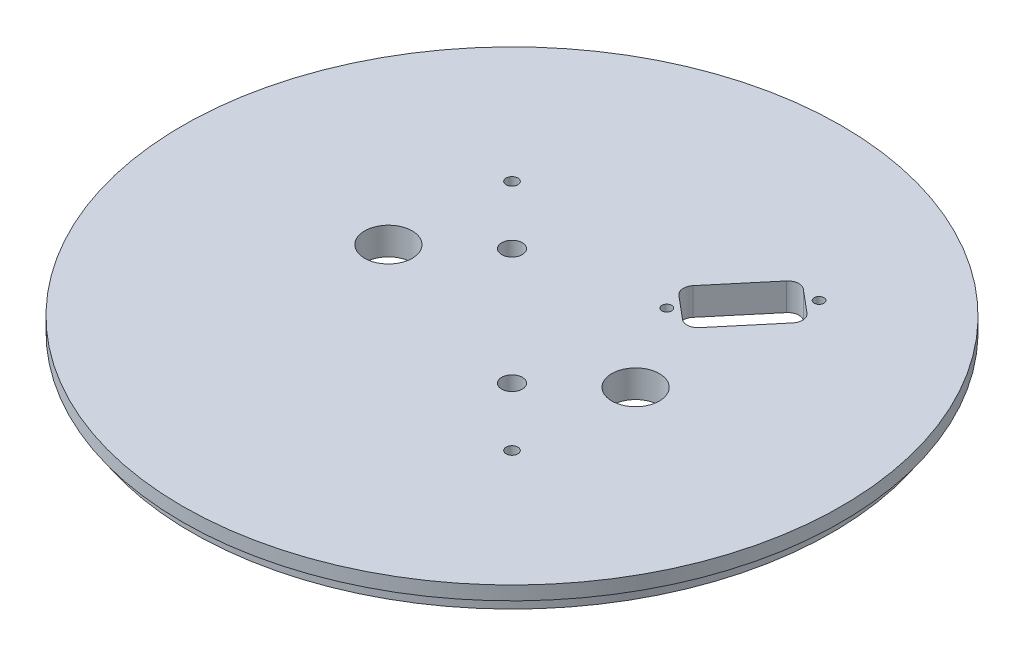
SolidWorks part; units mm, degrees
material "6061-T6 (SS)"
ref_plane "Front Plane" through (0, 0, 0) normal (0, 0, 1) x (1, 0, 0)
ref_plane "Top Plane" through (0, 0, 0) normal (0, 1, 0) x (1, 0, 0)
ref_plane "Right Plane" through (0, 0, 0) normal (1, 0, 0) x (0, 0, -1)
sketch "Sketch1" plane through (0, 0, 0) normal (0, 1, 0) x (1, 0, 0)
  line L0 (0, -76.2) -> (0, 76.2) construction
  line L1 (-76.2, 0) -> (76.2, 0) construction
  line L2 (-26.9408, 26.9408) -> (0, 0) construction
  line L3 (0, 56.7387) -> (0, 29.6936) construction
  line L4 (3.6407, 56.7387) -> (3.6407, 29.6936) construction
  line L5 (-3.6407, 56.7387) -> (-3.6407, 29.6936) construction
  line L6 (0, -56.7387) -> (0, -29.6936) construction
  line L7 (3.6407, -56.7387) -> (3.6407, -29.6936) construction
  line L8 (-3.6407, -56.7387) -> (-3.6407, -29.6936) construction
  line L9 (-53.8815, -53.8815) -> (54.3236, 54.3236) construction
  circle A0 centre (0, 0) radius 76.2
  circle A1 centre (0, 0) radius 3.175 construction
  circle A2 centre (28.575, 0) radius 5.5
  circle A3 centre (-28.575, 0) radius 5.5
  circle A4 centre (-26.9408, 26.9408) radius 1.3589
  arc A6 (3.6407, 56.7387) -> (-3.6407, 56.7387) centre (0, 56.7387) ccw construction
  arc A7 (-3.6407, 29.6936) -> (3.6407, 29.6936) centre (0, 29.6936) ccw construction
  arc A8 (3.6407, -56.7387) -> (-3.6407, -56.7387) centre (0, -56.7387) cw construction
  arc A9 (-3.6407, -29.6936) -> (3.6407, -29.6936) centre (0, -29.6936) cw construction
  circle A10 centre (26.9408, -26.9408) radius 1.3589
  circle A11 centre (-13.4704, 13.4704) radius 2.3813
  circle A12 centre (13.4704, -13.4704) radius 2.3813
  point P16 (0, 43.2162)
  point P19 (0, 0)
  point P26 (0, -43.2162)
  dimension "D1" = 152.4
  dimension "D2" = 6.35
  dimension "D3" = 11
  dimension "D5" = 2.7178
  dimension "D8" = 4.7625
  dimension "D6" = 38.1
  dimension "D7" = 45
  dimension "D4" = 45
  dimension "D9" = 28.575
extrude "Boss-Extrude1" add sketch "Sketch1" along normal blind 6.35
sketch "Sketch2" plane through (0, 0, 0) normal (0, -1, 0) x (1, 0, 0)
  circle A0 centre (0, 0) radius 76.2
  circle A1 centre (0, 0) radius 74.041
  dimension "D1" = 152.4
  dimension "D2" = 148.082
extrude "Cut-Extrude1" cut sketch "Sketch2" against normal blind 3.175
sketch "Sketch3" plane through (0, 6.35, 0) normal (0, 1, 0) x (1, 0, 0)
  line L0 (0, 76.2) -> (0, -76.2) construction
  line L1 (-76.2, 0) -> (76.2, 0) construction
  line L2 (0, 34.798) -> (0, 13.97) construction
  line L3 (3.2385, 34.798) -> (3.2385, 13.97)
  line L4 (-3.2385, 34.798) -> (-3.2385, 13.97)
  line L5 (0, -34.798) -> (0, -13.97) construction
  line L6 (3.2385, -34.798) -> (3.2385, -13.97)
  line L7 (-3.2385, -34.798) -> (-3.2385, -13.97)
  circle A0 centre (0, 0) radius 76.2 construction
  arc A1 (3.2385, 34.798) -> (-3.2385, 34.798) centre (0, 34.798) ccw
  arc A2 (-3.2385, 13.97) -> (3.2385, 13.97) centre (0, 13.97) ccw
  arc A3 (3.2385, -34.798) -> (-3.2385, -34.798) centre (0, -34.798) cw
  arc A4 (-3.2385, -13.97) -> (3.2385, -13.97) centre (0, -13.97) cw
  point P7 (0, 13.97)
  point P8 (0, 34.798)
  point P12 (0, 24.384)
  point P20 (0, -24.384)
  point P25 (0, -34.798)
  point P26 (0, -13.97)
  dimension "D1" = 13.97
  dimension "D2" = 20.828
  dimension "D3" = 6.477
extrude "Cut-Extrude2" cut sketch "Sketch3" against normal blind 3.556 from offset 5.969 offset against normal yes
hole_wizard "Tap Drill for #4-40 Tap1" positions "Sketch5" profile "Sketch6" hole size "#4-40" standard "ANSI Inch" end condition through all
sketch "Sketch5" plane through (0, 6.35, 0) normal (0, 1, 0) x (1, 0, 0)
  line L0 (0, 0) -> (53.6567, 63.9455) construction
  line L2 (0, 0) -> (28.575, 0) construction
  point P0 (16.3268, 19.4575)
  point P2 (32.3965, 38.6086)
  dimension "D1" = 50
  dimension "D2" = 25
  dimension "D3" = 25.4
sketch "Sketch6" plane through (16.3268, 6.35, -19.4575) normal (1, 0, 0) x (0, 0, 1)
  line L0 (0, 0) -> (0, 6.35)
  line L1 (0, 6.35) -> (1.1303, 6.35)
  line L2 (1.1303, 6.35) -> (1.1303, 0)
  line L5 (1.1303, 0) -> (0, 0)
  line L11 (0, -6.35) -> (0, 107.95) construction
  dimension "Thru Hole Dia." = 2.2606
  dimension "Thru Hole Depth" = 6.35
sketch "Sketch4" plane through (0, 6.35, 0) normal (0, 1, 0) x (1, 0, 0)
  line L0 (15.1695, 23.4128) -> (20.423, 19.0046)
  line L1 (14.8564, 26.9913) -> (24.7219, 38.7485)
  line L2 (24.0014, 19.3177) -> (33.8669, 31.0749)
  line L3 (28.3003, 39.0616) -> (33.5538, 34.6533)
  line L4 (0, 0) -> (32.3965, 38.6086) construction
  circle A1 centre (16.3268, 19.4575) radius 1.1303 construction
  arc A2 (24.7219, 38.7485) -> (28.3003, 39.0616) centre (26.6676, 37.1158) cw
  arc A3 (33.8669, 31.0749) -> (33.5538, 34.6533) centre (31.9212, 32.7076) ccw
  arc A4 (20.423, 19.0046) -> (24.0014, 19.3177) centre (22.0557, 20.9503) ccw
  arc A5 (14.8564, 26.9913) -> (15.1695, 23.4128) centre (16.8021, 25.3586) ccw
  point P11 (17.7962, 21.2087)
  dimension "D4" = 2.54
  dimension "D1" = 2.286
  dimension "D2" = 2.286
  dimension "D3" = 11.938
extrude "Cut-Extrude3" cut sketch "Sketch4" against normal through all
equation "\"leadDist\"=1.5"
equation "\"Lead_Screw_Dist\"= 2.25in"
equation "\"D9@Sketch1\"=\"Lead_Screw_Dist\"/2"
equation "\"Lead_Screw_Diam\"= 11mm"
equation "\"D3@Sketch1\"=\"Lead_Screw_Diam\""
equation "\"Bodytube_OD\"= 6.17in"
equation "\"Bodytube_ID\"= 5.998in"
equation "\"Motor_OD\"= 4in"
equation "\"Fwd_Tube_Length\"= 40in"
equation "\"Mid_Tube_Length\"= 1in"
equation "\"Aft_Section_Length\"= 39in"
equation "\"AB_Coupler_OD_Length\"= 1in"
equation "\"AB_Coupling_Section_Length\"= 0.375in"
equation "\"AB_Coupler_Length\"= \"AB_Coupler_OD_Length\" + \"AB_Coupling_Section_Length\" * 2"
equation "\"Cutout_Angle\"= 80"
equation "\"AB_Paddle_Height\"= 0.375in"
equation "\"AB_Coupler_Num_Screws\"= 6"
equation "\"Num_Cutouts\"= 3"
equation "\"AB_Coupler_OD\"= 6.17in"
equation "\"AB_Coupler_ID\"= 5.75in"
equation "\"AB_Coupler_Surface_Diameter\"= 5.998in"
equation "\"AB_Coupling_Screw_Diameter\"= 0.1065in"
equation "\"AB_Central_Bushing_Length\"= .75in"
equation "\"Lead_Screw_Length\"= (\"Mid_Coupler_Length\" + 2*0.375in + 2*0.5in)"
equation "\"Paddle_Pin_Offset\"= .25in"
equation "\"Paddle_Pin_Radius\"= 2.25in"
equation "\"SS_Paddle_Pin_Radius\"= 2.25*0.66in"
equation "\"Paddle_Gear_OD\"= 3.2in"
equation "\"Drive_Gear_OD\"= 1.7in"
equation "\"Fwd_BKHD_From_Top\"= 18in"
equation "\"Fin_Thickness\"= .118in"
equation "\"Guiderail_Cutout_Diameter\"= 1.5in"
equation "\"DB9_Hole_Dist\"= 25mm"
equation "\"Airbrakes_Wire_Hole_Dia\"= .25in"
equation "\"Airbrakes_Wire_Hole_Dist\"= 1.1in"
equation "\"Servo_Gear_Offset\"= 0.5in"
equation "\"Mid_Coupler_Length\"= 13in"
equation "\"D2@Sketch5\"=\"DB9_Hole_Dist\""
equation "\"DB9_Relief_Width\"= 0.47in"
equation "\"DB9_Relief_Hole_Offset\"= 0.09in"
equation "\"D1@Sketch4\"=\"DB9_Relief_Hole_Offset\""
equation "\"D2@Sketch4\"=\"DB9_Relief_Hole_Offset\""
equation "\"D3@Sketch4\"=\"DB9_Relief_Width\""
